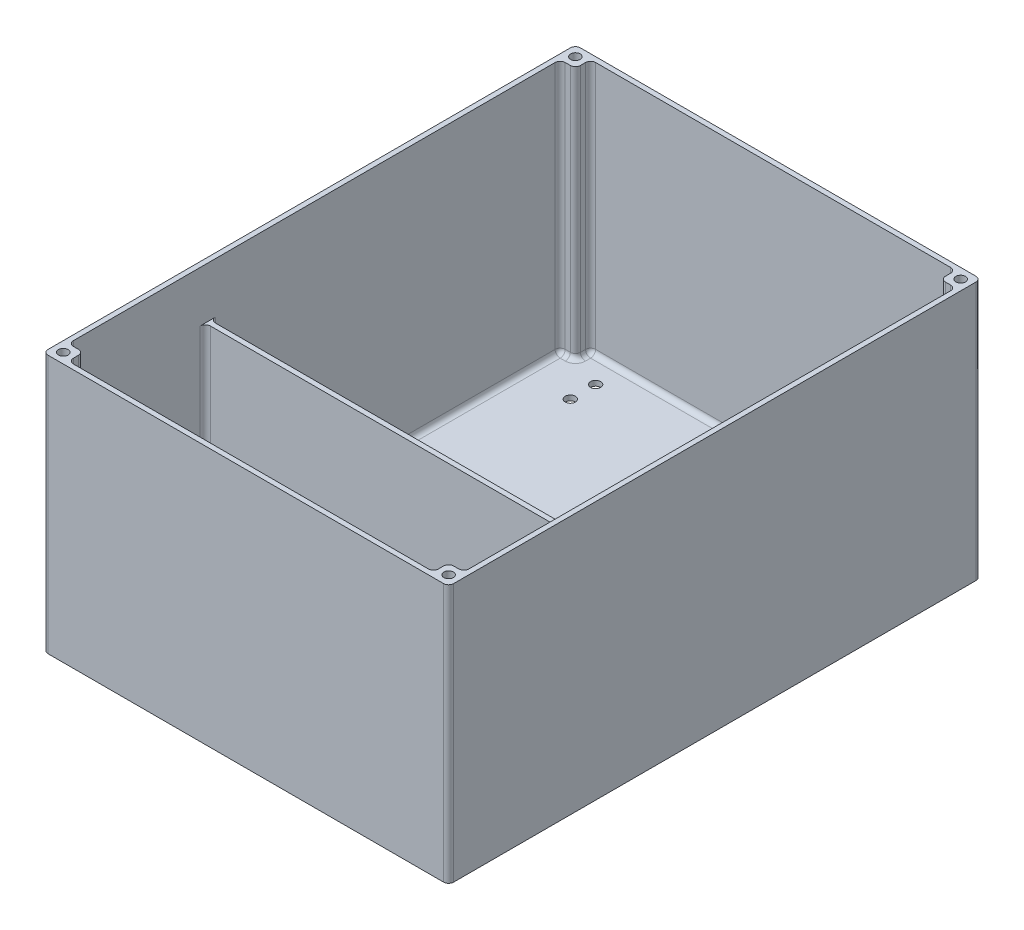
SolidWorks part; units mm, degrees
ref_plane "Front Plane" through (0, 0, 0) normal (0, 0, 1) x (1, 0, 0)
ref_plane "Top Plane" through (0, 0, 0) normal (0, 1, 0) x (1, 0, 0)
ref_plane "Right Plane" through (0, 0, 0) normal (1, 0, 0) x (0, 0, -1)
sketch "Sketch1" plane through (0, 0, 0) normal (0, 1, 0) x (1, 0, 0)
  line L1 (0, 0) -> (160, 0)
  line L2 (0, 0) -> (0, 210)
  line L3 (0, 210) -> (160, 210)
  line L4 (160, 0) -> (160, 210)
  dimension "D1" = 160
  dimension "D2" = 210
extrude "Boss-Extrude3" add sketch "Sketch1" along normal blind 2
sketch "Sketch3" plane through (0, 2, 0) normal (0, 1, 0) x (1, 0, 0)
  line L5 (0, 210) -> (160, 210)
  line L6 (0, 210) -> (0, 0)
  line L7 (0, 0) -> (160, 0)
  line L8 (2, 208) -> (2, 2)
  line L9 (2, 2) -> (158, 2)
  line L10 (158, 2) -> (158, 208)
  line L11 (158, 208) -> (2, 208)
  line L12 (2, 202) -> (2, 8)
  line L13 (8, 2) -> (152, 2)
  line L14 (158, 8) -> (158, 202)
  line L15 (152, 208) -> (8, 208)
  line L16 (160, 210) -> (160, 0)
  line L19 (2, 202) -> (8, 202)
  line L20 (8, 208) -> (8, 202)
  line L23 (158, 202) -> (152, 202)
  line L24 (152, 208) -> (152, 202)
  line L27 (2, 8) -> (8, 8)
  line L28 (8, 2) -> (8, 8)
  line L31 (158, 8) -> (152, 8)
  line L32 (152, 2) -> (152, 8)
  dimension "D2" = 6
  dimension "D1" = 2
extrude "Boss-Extrude4" add sketch "Sketch3" along normal blind 100
ref_plane "Plane1" through (80, 0, 0) normal (1, 0, 0) x (0, 0, -1)
ref_plane "Plane2" through (0, 0, -105) normal (0, 0, 1) x (1, 0, 0)
fillet "Fillet1" radius 2 16 edges at (160, 51, -210) (160, 51, 0) (0, 51, 0) (0, 51, -210) (2, 52, -8) (8, 52, -8) (8, 52, -2) (152, 52, -2) (152, 52, -8) (158, 52, -8) (158, 52, -202) (152, 52, -202) (152, 52, -208) (8, 52, -202) (8, 52, -208) (2, 52, -202)
sketch "Sketch4" plane through (0, 102, 0) normal (0, 1, 0) x (1, 0, 0)
  line L0 (4, 206) -> (4, 210) construction
  line L1 (158, 210) -> (2, 210) construction
  line L2 (4, 206) -> (0, 206) construction
  line L3 (0, 208) -> (0, 2) construction
  line L4 (80, -56.1) -> (80, 56.1) construction
  line L5 (156, 206) -> (160, 206) construction
  line L6 (156, 206) -> (156, 210) construction
  line L7 (-56.1, 105) -> (56.1, 105) construction
  line L8 (156, 4) -> (156, 0) construction
  line L9 (156, 4) -> (160, 4) construction
  line L10 (4, 4) -> (0, 4) construction
  line L11 (4, 4) -> (4, 0) construction
  circle A0 centre (4, 206) radius 1.9
  circle A1 centre (156, 206) radius 1.9
  circle A2 centre (156, 4) radius 1.9
  circle A3 centre (4, 4) radius 1.9
  dimension "D3" = 3.8
  dimension "D1" = 4
  dimension "D2" = 4
extrude "Cut-Extrude1" cut sketch "Sketch4" against normal blind 10
sketch "Sketch5" plane through (0, 2, 0) normal (0, 1, 0) x (1, 0, 0)
  line L0 (20, 198) -> (140, 198) construction
  line L1 (140, 198) -> (140, 188) construction
  line L2 (140, 188) -> (20, 188) construction
  line L3 (20, 188) -> (20, 198) construction
  line L4 (-56.1, 105) -> (56.1, 105) construction
  line L5 (20, 198) -> (2, 198) construction
  line L6 (2, 200) -> (2, 10) construction
  line L7 (140, 198) -> (158, 198) construction
  line L8 (158, 10) -> (158, 200) construction
  circle A0 centre (20, 198) radius 2
  circle A1 centre (140, 198) radius 2
  circle A2 centre (140, 188) radius 2
  circle A3 centre (20, 188) radius 2
  circle A4 centre (20, 22) radius 2
  circle A5 centre (140, 22) radius 2
  circle A6 centre (140, 12) radius 2
  circle A7 centre (20, 12) radius 2
  dimension "D5" = 4
  dimension "D1" = 120
  dimension "D2" = 10
  dimension "D4" = 10
extrude "Cut-Extrude2" cut sketch "Sketch5" against normal blind 10
sketch "Sketch6" plane through (0, 2, 0) normal (0, 1, 0) x (1, 0, 0)
  line L0 (2, 200) -> (2, 10) construction
  line L1 (2, 64) -> (158, 64)
  line L2 (2, 64) -> (2, 62)
  line L3 (2, 62) -> (158, 62)
  line L4 (158, 64) -> (158, 62)
  line L5 (158, 10) -> (158, 200) construction
  line L6 (10, 2) -> (150, 2) construction
  dimension "D1" = 2
  dimension "D2" = 60
extrude "Boss-Extrude5" add sketch "Sketch6" along normal blind 80
fillet "Fillet2" radius 2 32 edges at (158, 2, -36) (157.4142, 2, -8.5858) (155, 2, -8) (152.5858, 2, -7.4142) (152, 2, -5) (151.4142, 2, -2.5858) (80, 2, -2) (8.5858, 2, -2.5858) (8, 2, -5) (7.4142, 2, -7.4142) (5, 2, -8) (2.5858, 2, -8.5858) (158, 2, -132) (157.4142, 2, -201.4142) (155, 2, -202) (152.5858, 2, -202.5858) (152, 2, -205) (151.4142, 2, -207.4142) (80, 2, -208) (8.5858, 2, -207.4142) (8, 2, -205) (7.4142, 2, -202.5858) (5, 2, -202) (2.5858, 2, -201.4142) (2, 2, -36) (2, 42, -62) (80, 2, -62) (158, 42, -62) (158, 42, -64) (2, 42, -64) (80, 2, -64) (2, 2, -132)
